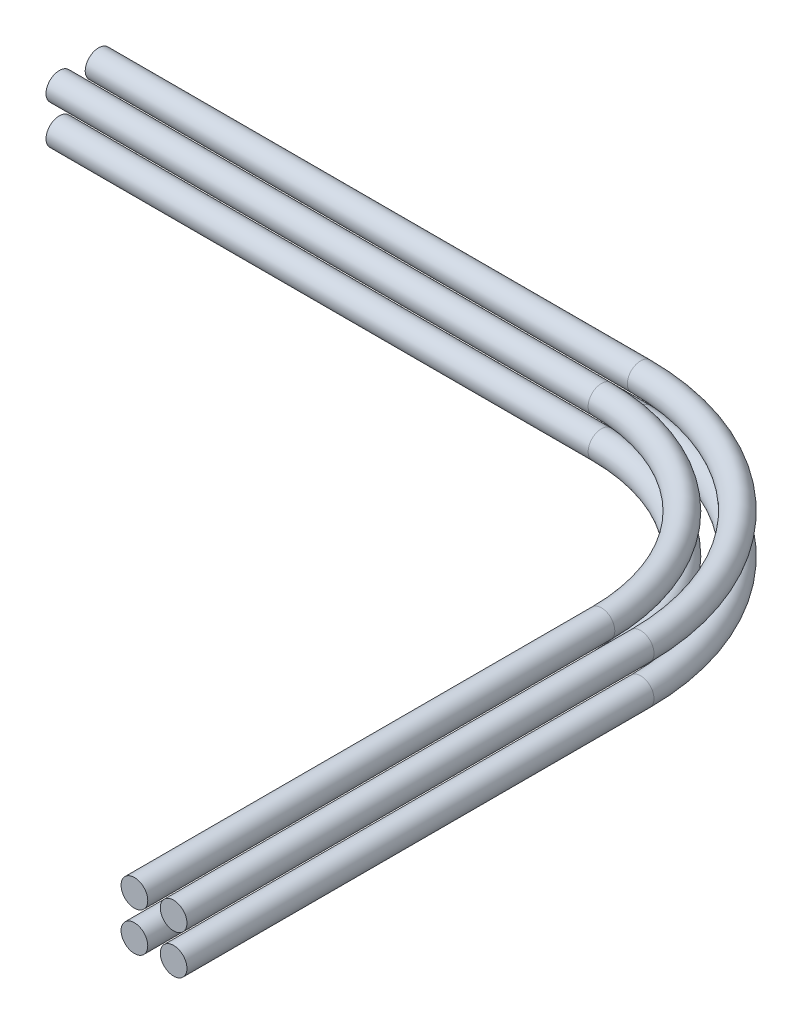
SolidWorks part; units mm, degrees
ref_plane "Front Plane" through (0, 0, 0) normal (0, 0, 1) x (1, 0, 0)
ref_plane "Top Plane" through (0, 0, 0) normal (0, 1, 0) x (1, 0, 0)
ref_plane "Right Plane" through (0, 0, 0) normal (1, 0, 0) x (0, 0, -1)
sketch "Sketch1" plane through (0, 0, 0) normal (0, 1, 0) x (1, 0, 0)
  line L0 (0, 0) -> (65, 0)
  line L1 (93, -28) -> (93, -84)
  line L2 (0, -4.7) -> (65, -4.7)
  line L3 (88.3, -28) -> (88.3, -84)
  line L4 (0, -4.7) -> (0, 0) construction
  line L5 (93, -84) -> (88.3, -84) construction
  line L6 (65, 0) -> (65, -4.7) construction
  line L7 (88.3, -28) -> (93, -28) construction
  arc A0 (65, -4.7) -> (88.3, -28) centre (65, -28) cw
  arc A1 (65, 0) -> (93, -28) centre (65, -28) cw
  point P11 (93, 0)
  dimension "D4" = 28
  dimension "D1" = 4.7
  dimension "D2" = 65
  dimension "D3" = 84
ref_plane "Plane1" through (0, 0, 0) normal (1, 0, 0) x (0, 0, -1)
sketch "Sketch2" plane through (0, 0, 0) normal (1, 0, 0) x (0, 0, -1)
  circle A0 centre (0, 0) radius 1.6
  circle A1 centre (-4.7, 0) radius 1.6
  dimension "D1" = 3.2
sweep "Sweep1" add profiles "Sketch2" path "Sketch1"
sketch "Sketch3" plane through (0, 0, 0) normal (1, 0, 0) x (0, 0, -1)
  line L0 (0, 0) -> (0, 4.7) construction
  dimension "D1" = 4.7
pattern_linear "LPattern1" count 2 spacing 4.7 along (0, 1, 0) of "Sweep1"
